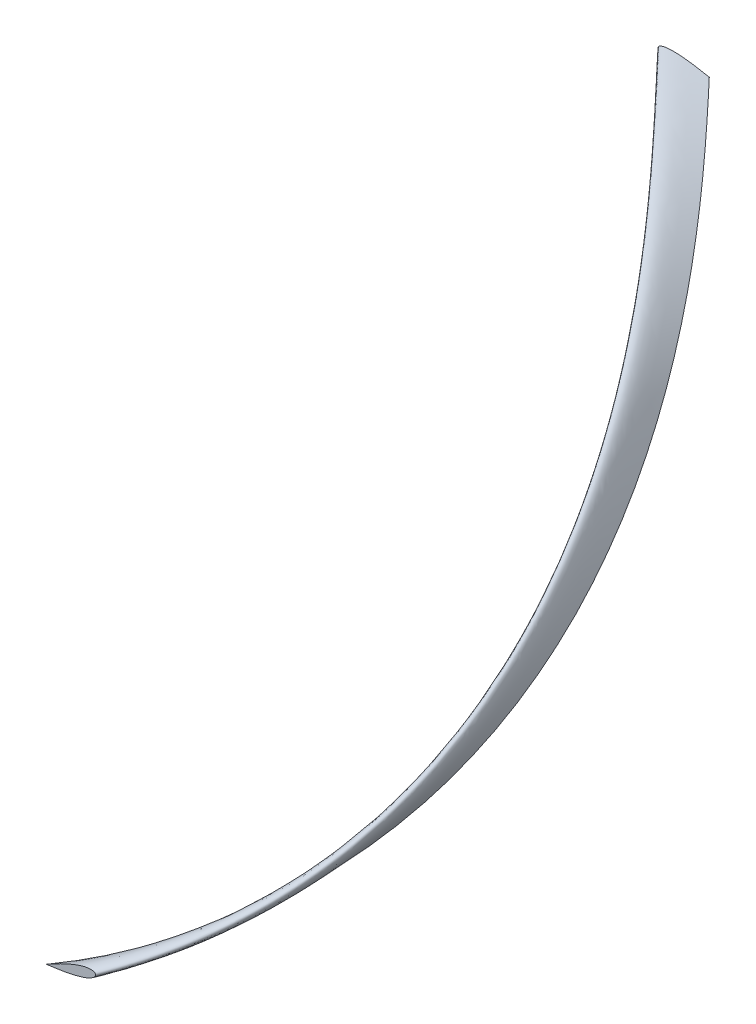
SolidWorks part; units mm, degrees
ref_plane "Front Plane" through (0, 0, 0) normal (0, 0, 1) x (1, 0, 0)
ref_plane "Top Plane" through (0, 0, 0) normal (0, 1, 0) x (1, 0, 0)
ref_plane "Right Plane" through (0, 0, 0) normal (1, 0, 0) x (0, 0, -1)
curve "Curve1"
  spline degree 3 poles (1, 0.0019, 0) (0.9833, 0.0053, 0) (0.9501, 0.0122, 0) (0.8834, 0.025, 0) (0.8002, 0.0397, 0) (0.7001, 0.0553, 0) (0.6002, 0.0688, 0) (0.5002, 0.0799, 0) (0.4001, 0.0878, 0) (0.3167, 0.0906, 0) (0.25, 0.0895, 0) (0.1999, 0.0865, 0) (0.1497, 0.0808, 0) (0.1079, 0.0728, 0) (0.0746, 0.0633, 0) (0.0492, 0.0537, 0) (0.0279, 0.0421, 0) (0.0083, 0.0261, 0) (-0.0054, 0, 0) (0.0083, -0.0261, 0) (0.0279, -0.0421, 0) (0.0492, -0.0537, 0) (0.0746, -0.0633, 0) (0.1079, -0.0728, 0) (0.1497, -0.0808, 0) (0.1999, -0.0865, 0) (0.25, -0.0895, 0) (0.3167, -0.0906, 0) (0.4001, -0.0878, 0) (0.5002, -0.0799, 0) (0.6002, -0.0688, 0) (0.7001, -0.0553, 0) (0.8002, -0.0397, 0) (0.8834, -0.025, 0) (0.9501, -0.0122, 0) (0.9833, -0.0053, 0) (1, -0.0019, 0) knots 0 0 0 0 0.024604 0.049152 0.098109 0.146905 0.195555 0.244056 0.29241 0.340644 0.364754 0.388906 0.413178 0.437756 0.450305 0.46323 0.477068 0.485036 0.5 0.514964 0.522932 0.53677 0.549695 0.562244 0.586822 0.611094 0.635246 0.659356 0.70759 0.755944 0.804445 0.853095 0.901891 0.950848 0.975396 1 1 1 1
sketch "Sketch1" plane through (0, 0, 0) normal (0, 0, 1) x (1, 0, 0)
  line L0 (0, 0) -> (35, 0) construction
  line L1 (35, 0.0661) -> (35, -0.0661)
  line L2 (10.15, 0) -> (10.15, 3.1499) construction
  circle A0 centre (10.15, -150) radius 150 construction
  spline S1 degree 3 poles (35, 0.0661) (34.417, 0.1867) (33.2522, 0.4275) (30.9204, 0.8742) (28.0057, 1.388) (24.5052, 1.9349) (21.0053, 2.4095) (17.5054, 2.7977) (14.0046, 3.0728) (11.0838, 3.1706) (8.7486, 3.1316) (6.9958, 3.0278) (5.2396, 2.8274) (3.778, 2.5473) (2.6122, 2.2143) (1.722, 1.8778) (0.9763, 1.4726) (0.2904, 0.9121) (-0.1895, 0) (0.2904, -0.9121) (0.9763, -1.4726) (1.722, -1.8778) (2.6122, -2.2143) (3.778, -2.5473) (5.2396, -2.8274) (6.9958, -3.0278) (8.7486, -3.1316) (11.0838, -3.1706) (14.0046, -3.0728) (17.5054, -2.7977) (21.0053, -2.4095) (24.5052, -1.9349) (28.0057, -1.388) (30.9204, -0.8742) (33.2522, -0.4275) (34.417, -0.1867) (35, -0.0661) knots 0 0 0 0 0.024604 0.049152 0.098109 0.146905 0.195555 0.244056 0.29241 0.340644 0.364754 0.388906 0.413178 0.437756 0.450305 0.46323 0.477068 0.485036 0.5 0.514964 0.522932 0.53677 0.549695 0.562244 0.586822 0.611094 0.635246 0.659356 0.70759 0.755944 0.804445 0.853095 0.901891 0.950848 0.975396 1 1 1 1
  dimension "D3" = 300
  dimension "D1" = 35
  dimension "D2" = 10.15
ref_plane "Plane1" through (0, 0, 0) normal (0, 0, 1) x (1, 0, 0)
sketch "Sketch2" plane through (0, 0, 0) normal (0, 0, 1) x (1, 0, 0)
  circle A0 centre (10.15, -150) radius 150 construction
  circle A1 centre (10.15, -150) radius 150
  dimension "D1" = 300
curve "Helix/Spiral1" pitch 1000 height 450 radius 150 left hand yes centre (10.15, -150, 0) axis (0, 0, 1) start towards (0, 1, 0)
sweep "Sweep1" add profiles "Sketch1" path "Helix/Spiral1"
ref_axis "Axis1" through (10.15, -150, 0) along (0, 0, 1)
